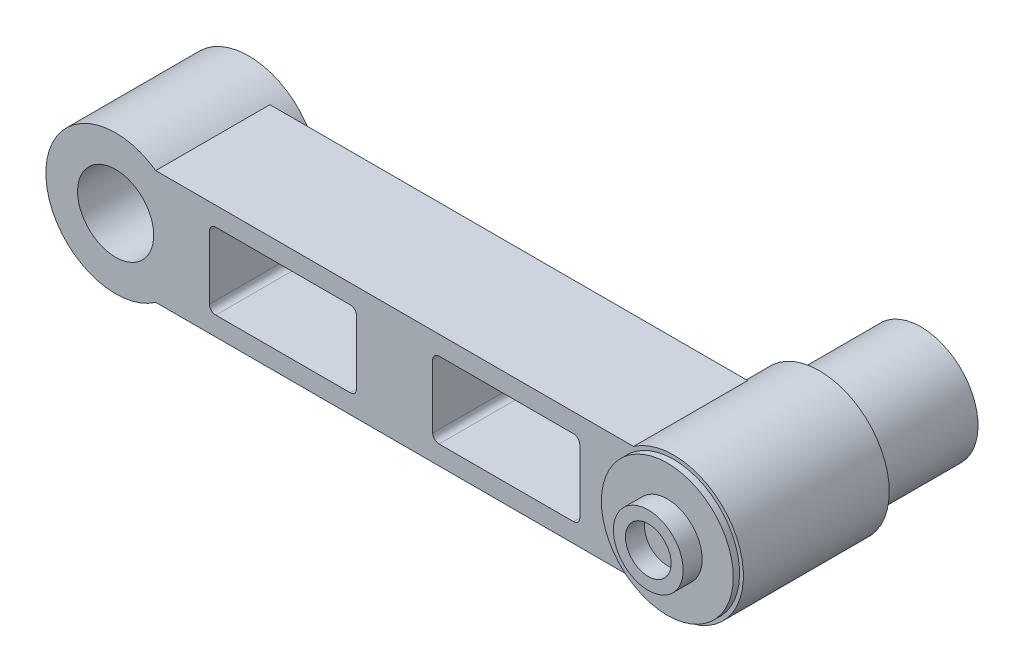
SolidWorks part; units mm, degrees
material "Cast Stainless Steel"
ref_plane "Front Plane" through (0, 0, 0) normal (0, 0, 1) x (1, 0, 0)
ref_plane "Top Plane" through (0, 0, 0) normal (0, 1, 0) x (1, 0, 0)
ref_plane "Right Plane" through (0, 0, 0) normal (1, 0, 0) x (0, 0, -1)
other "Center of Mass"
sketch "Sketch11" plane through (0, 0, 0) normal (0, 0, 1) x (1, 0, 0)
  line L0 (0, 440) -> (0, 0) construction
  line L1 (45, 31.6228) -> (45, 408.3772)
  line L4 (-45, 31.6228) -> (-45, 408.3772)
  circle A0 centre (0, 0) radius 55
  circle A1 centre (0, 440) radius 55
  dimension "D1" = 110
  dimension "D2" = 110
  dimension "D3" = 45
  dimension "D4" = 45
  dimension "D5" = 440
extrude "Boss-Extrude5" add sketch "Sketch11" along normal blind 90 contours A1 L4 A0 L1 | L0 A1 L4 A0 | A1 | A0 region at (22.9783, 220, 0) region at (-22.9783, 220, 0) region at (-24.6378, 392.5734, 0) region at (24.6378, 47.4266, 0)
extrude "Boss-Extrude6" add sketch "Sketch11<3>" along normal blind 115 contours A1 region at (0, 440, 0)
sketch "Sketch11<3>" plane through (0, 0, 0) normal (0, 0, 1) x (1, 0, 0) same geometry as "Sketch11"
extrude "Boss-Extrude7" add sketch "Sketch11<4>" along normal blind 105 contours A0 region at (0, 0, 0)
sketch "Sketch11<4>" plane through (0, 0, 0) normal (0, 0, 1) x (1, 0, 0) same geometry as "Sketch11"
sketch "Sketch13" plane through (0, 0, 90) normal (0, 0, 1) x (1, 0, 0)
  line L2 (7.6389, 82) -> (7.6389, 54.4669)
  line L3 (7.6389, 54.4669) -> (-7.6389, 54.4669)
  line L4 (-7.6389, 82) -> (-7.6389, 54.4669)
  arc A1 (7.6389, 82) -> (-7.6389, 82) centre (0, 82) ccw
  arc A2 (45, 31.6228) -> (-45, 31.6228) centre (0, 0) ccw construction
extrude "Boss-Extrude8" add sketch "Sketch13" along normal blind 15
sketch "Sketch17" plane through (0, 0, 115) normal (0, 0, 1) x (1, 0, 0)
  circle A0 centre (0, 440) radius 45
extrude "Boss-Extrude9" add sketch "Sketch17" along normal blind 80
sketch "Sketch18" plane through (0, 0, 0) normal (0, 0, -1) x (-1, 0, 0)
  circle A0 centre (0, 440) radius 52
extrude "Boss-Extrude10" add sketch "Sketch18" along normal blind 5
sketch "Sketch19" plane through (0, 0, -5) normal (0, 0, -1) x (-1, 0, 0)
  circle A0 centre (0, 440) radius 37.5
  circle A1 centre (0, 440) radius 27.5
  circle A2 centre (0, 440) radius 18
extrude "Boss-Extrude12" add sketch "Sketch19" along normal blind 15 contours A2 | A1
ref_plane "Plane1" through (0, 0, 167.63) normal (0, 0, -1) x (-1, 0, 0)
move or copy body "Body-Move/Copy2" bodies to move or copy 113 copy no rotation origin (0, 0, 0) rotation axis (0, 1, 0) rotation angle 180
sketch "Sketch28" plane through (0, 0, -105) normal (0, 0, -1) x (-1, 0, 0)
  circle A0 centre (0, 0) radius 52
  dimension "D1" = 104
extrude "Cut-Extrude2" cut sketch "Sketch28" against normal blind 60
ref_plane "Plane2" through (0, 0, 10) normal (0, 0, 1) x (1, 0, 0)
sketch "Sketch29" plane through (0, 0, 0) normal (0, 0, 1) x (1, 0, 0)
  line L0 (-30, 250) -> (-30, 190) construction
  line L1 (-25, 190) -> (25, 190)
  line L2 (-30, 185) -> (-30, 79)
  line L3 (-25, 74) -> (25, 74)
  line L4 (30, 185) -> (30, 79)
  line L5 (-25, 366) -> (25, 366)
  line L6 (45, 31.6228) -> (45, 408.3772)
  line L7 (-45, 408.3772) -> (-45, 31.6228)
  line L8 (45, 31.6228) -> (45, 408.3772)
  line L9 (-45, 408.3772) -> (-45, 31.6228)
  line L10 (-30, 361) -> (-30, 255)
  line L11 (-25, 250) -> (25, 250)
  line L12 (30, 361) -> (30, 255)
  line L13 (-30, 220) -> (103.3616, 220) construction
  line L14 (0, 440) -> (0, 0) construction
  arc A0 (25, 250) -> (30, 255) centre (25, 255) ccw
  arc A1 (-25, 250) -> (-30, 255) centre (-25, 255) cw
  arc A2 (-45, 31.6228) -> (45, 31.6228) centre (0, 0) ccw
  arc A3 (45, 408.3772) -> (-45, 408.3772) centre (0, 440) ccw
  arc A4 (-45, 31.6228) -> (45, 31.6228) centre (0, 0) ccw
  arc A5 (45, 408.3772) -> (-45, 408.3772) centre (0, 440) ccw
  arc A6 (30, 361) -> (25, 366) centre (25, 361) ccw
  arc A7 (-30, 361) -> (-25, 366) centre (-25, 361) cw
  arc A8 (30, 79) -> (25, 74) centre (25, 79) cw
  arc A9 (-30, 79) -> (-25, 74) centre (-25, 79) ccw
  arc A10 (30, 185) -> (25, 190) centre (25, 185) ccw
  arc A11 (-30, 185) -> (-25, 190) centre (-25, 185) cw
  point P26 (-30, 366)
  point P29 (30, 74)
  point P32 (-30, 74)
  dimension "D5" = 5
  dimension "D6" = 5
  dimension "D2" = 116
  dimension "D3" = 60
  dimension "D4" = 60
  dimension "D1" = 0
extrude "Cut-Extrude3" cut sketch "Sketch29" against normal offset from surface (80 mm away) 10 contours A7 L10 A1 L11 A0 L12 A6 L5 | A11 L2 A9 L3 A8 L4 A10 L1 region at (0, 132, 0) region at (0, 308, 0) up to face at (0, 143.1191, -90)
sketch "Sketch31" plane through (0, 0, 0) normal (0, 0, 1) x (1, 0, 0)
  line L2 (45, 31.6228) -> (45, 408.3772)
  line L3 (-45, 408.3772) -> (-45, 31.6228)
  line L4 (45, 31.6228) -> (45, 408.3772)
  line L5 (-45, 408.3772) -> (-45, 31.6228)
  circle A0 centre (0, 0) radius 30
  arc A2 (-45, 31.6228) -> (45, 31.6228) centre (0, 0) ccw
  arc A3 (45, 408.3772) -> (-45, 408.3772) centre (0, 440) ccw
  arc A4 (-45, 31.6228) -> (45, 31.6228) centre (0, 0) ccw
  arc A5 (45, 408.3772) -> (-45, 408.3772) centre (0, 440) ccw
  dimension "D2" = 60
  dimension "D1" = 0
extrude "Cut-Extrude6" cut sketch "Sketch31" against normal through all contours A0 region at (0, 0, 0)
move or copy body "Body-Move/Copy3" bodies to move or copy 124 copy no rotation origin (0, 0, -87.5) rotation axis (0, 1, 0) rotation angle 180
move or copy body "Body-Move/Copy4" bodies to move or copy 125 copy no rotation origin (0, 225, 0) rotation axis (0, 0, -1) rotation angle 90
move or copy body "Body-Move/Copy6" bodies to move or copy 126 copy no rotation origin (225, 0, -17.5) rotation axis (0, 1, 0) rotation angle 180
sketch "Sketch33" plane through (0, 0, 35) normal (0, 0, -1) x (-1, 0, 0)
  line L2 (-620.5331, 217.3611) -> (-593, 217.3611)
  line L3 (-593, 232.6389) -> (-620.5331, 232.6389)
  line L4 (-620.5331, 217.3611) -> (-593, 217.3611)
  line L5 (-593, 232.6389) -> (-620.5331, 232.6389)
  arc A2 (-620.5331, 232.6389) -> (-620.5331, 217.3611) centre (-675, 225) ccw
  arc A3 (-593, 217.3611) -> (-593, 232.6389) centre (-593, 225) ccw
  arc A4 (-620.5331, 232.6389) -> (-620.5331, 217.3611) centre (-675, 225) ccw
  arc A5 (-593, 217.3611) -> (-593, 232.6389) centre (-593, 225) ccw
  point P5 (-675, 225)
  dimension "D1" = 0
move or copy body "Body-Move/Copy7" bodies to move or copy 128 copy no translate (-675, -225, -35)
move or copy body "Body-Move/Copy8" bodies to move or copy 129 copy no rotation origin (-225, 0, 0) rotation axis (0, 0, -1) rotation angle 90
move or copy body "Body-Move/Copy9" bodies to move or copy 130 copy no rotation origin (-225, 0, 0) rotation axis (0, 0, -1) rotation angle 90
sketch "Sketch34" plane through (0, 0, 0) normal (0, 0, -1) x (-1, 0, 0)
  line L2 (395.5331, 7.6389) -> (368, 7.6389)
  line L3 (368, -7.6389) -> (395.5331, -7.6389)
  line L4 (395.5331, 7.6389) -> (368, 7.6389)
  line L5 (368, -7.6389) -> (395.5331, -7.6389)
  arc A2 (395.5331, -7.6389) -> (395.5331, 7.6389) centre (450, 0) ccw
  arc A3 (368, 7.6389) -> (368, -7.6389) centre (368, 0) ccw
  arc A4 (395.5331, -7.6389) -> (395.5331, 7.6389) centre (450, 0) ccw
  arc A5 (368, 7.6389) -> (368, -7.6389) centre (368, 0) ccw
  point P0 (208.8383, -418.5805)
  point P5 (450, 0)
  dimension "D1" = 0
move or copy body "Body-Move/Copy10" bodies to move or copy 131 copy no translate (450, 0, 0)
ref_axis "Axis2" through (0, 0, 0) along (0, 0, 1)
ref_plane "Plane10" through (0, 0, -62.63) normal (0, 0, -1) x (-1, 0, 0)
ref_point "Point3"
move or copy body "Body-Move/Copy14" bodies to move or copy 132 copy no translate (0, 0, 62.63)
